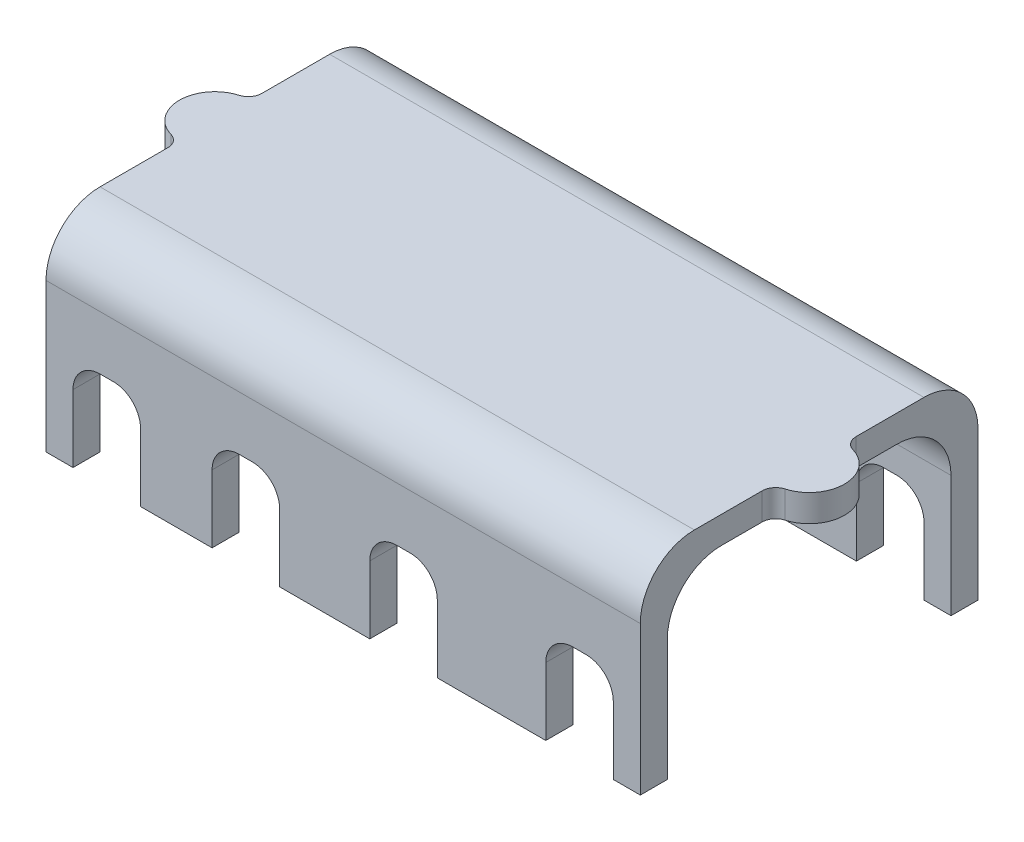
SolidWorks part; units mm, degrees
ref_plane "Plano frontal" through (0, 0, 0) normal (0, 0, 1) x (1, 0, 0)
ref_plane "Plano superior" through (0, 0, 0) normal (0, 1, 0) x (1, 0, 0)
ref_plane "Plano direito" through (0, 0, 0) normal (1, 0, 0) x (0, 0, -1)
sketch "Esboço1" plane through (0, 0, 0) normal (0, 1, 0) x (1, 0, 0)
  line L1 (-22, -12.5) -> (22, -12.5)
  line L2 (-22, -12.5) -> (-22, 12.5)
  line L3 (-22, 12.5) -> (22, 12.5)
  line L4 (22, -12.5) -> (22, 12.5)
  line L5 (-22, -12.5) -> (22, 12.5) construction
  line L6 (-22, 12.5) -> (22, -12.5) construction
  point P0 (0, 0)
  dimension "D1" = 44
  dimension "D2" = 25
extrude "Ressalto-extrusão1" add sketch "Esboço1" along normal mid plane 15
shell "Casca1" thickness 2 removed face at (0, -7.5, 0) removed face at (-22, 0, 0) removed face at (22, 0, 0)
sketch "Esboço2" plane through (0, 0, 12.5) normal (0, 0, 1) x (1, 0, 0)
  line L0 (22, 7.5) -> (22, -7.5) construction
  line L5 (-9.7033, -14.5) -> (-4.7033, -14.5)
  line L6 (-9.7033, -14.5) -> (-9.7033, -0.5)
  line L7 (-22, -7.5) -> (22, -7.5) construction
  line L8 (-20, -14.5) -> (-15, -14.5)
  line L9 (-20, -14.5) -> (-20, -0.5)
  line L10 (-20, -0.5) -> (-15, -0.5)
  line L11 (-15, -14.5) -> (-15, -0.5)
  line L12 (-20, -14.5) -> (-15, -0.5) construction
  line L13 (-20, -0.5) -> (-15, -14.5) construction
  line L14 (-22, 7.5) -> (-22, -7.5) construction
  line L15 (-9.7033, -0.5) -> (-4.7033, -0.5)
  line L16 (-4.7033, -14.5) -> (-4.7033, -0.5)
  line L17 (-9.7033, -14.5) -> (-4.7033, -0.5) construction
  line L18 (-9.7033, -0.5) -> (-4.7033, -14.5) construction
  line L19 (1.9702, -14.5) -> (6.9702, -14.5)
  line L20 (1.9702, -14.5) -> (1.9702, -0.5)
  line L21 (1.9702, -0.5) -> (6.9702, -0.5)
  line L22 (6.9702, -14.5) -> (6.9702, -0.5)
  line L23 (1.9702, -14.5) -> (6.9702, -0.5) construction
  line L24 (1.9702, -0.5) -> (6.9702, -14.5) construction
  line L25 (15, -14.5) -> (20, -14.5)
  line L26 (15, -14.5) -> (15, -0.5)
  line L27 (15, -0.5) -> (20, -0.5)
  line L28 (20, -14.5) -> (20, -0.5)
  line L29 (15, -14.5) -> (20, -0.5) construction
  line L30 (15, -0.5) -> (20, -14.5) construction
  point P0 (-17.5, -7.5)
  point P9 (-7.2033, -7.5)
  point P14 (4.4702, -7.5)
  point P19 (17.5, -7.5)
  dimension "D2" = 5
  dimension "D3" = 7
  dimension "D1" = 2
  dimension "D4" = 2
extrude "Corte-extrusão1" cut sketch "Esboço2" against normal through all
fillet "Filete1" radius 2 16 edges at (15, -0.5, 11.5) (15, -0.5, -11.5) (20, -0.5, 11.5) (20, -0.5, -11.5) (1.9702, -0.5, 11.5) (1.9702, -0.5, -11.5) (6.9702, -0.5, 11.5) (6.9702, -0.5, -11.5) (-9.7033, -0.5, 11.5) (-9.7033, -0.5, -11.5) (-4.7033, -0.5, 11.5) (-4.7033, -0.5, -11.5) (-15, -0.5, 11.5) (-15, -0.5, -11.5) (-20, -0.5, -11.5) (-20, -0.5, 11.5)
fillet "Filete2" radius 4 4 edges at (0, 7.5, -12.5) (0, 7.5, 12.5) (0, 5.5, 10.5) (0, 5.5, -10.5)
sketch "Esboço5" plane through (0, 7.5, 0) normal (0, 1, 0) x (1, 0, 0)
  line L0 (-22, -1.619) -> (-22, -2.619)
  line L1 (-22, -2.619) -> (-22, -1.619)
  line L2 (-22, 1.619) -> (-22, 2.619)
  line L3 (-22, 8.5) -> (-22, -8.5) construction
  line L4 (-22, -1.619) -> (-22, 1.619)
  line L5 (0, -8.25) -> (0, 8.25) construction
  line L6 (22, -1.619) -> (22, 1.619)
  line L7 (22, 1.619) -> (22, 2.619)
  line L8 (22, -2.619) -> (22, -1.619)
  line L9 (22, -1.619) -> (22, -2.619)
  arc A0 (-22, 2.619) -> (-22, -2.619) centre (-22, 0) ccw
  arc A2 (22, 2.619) -> (22, -2.619) centre (22, 0) cw
  line M10 (22, -8.5) -> (22, 8.5)
  line M12 (-22, 8.5) -> (-22, -8.5)
extrude "Ressalto-extrusão4" add sketch "Esboço5" against normal up to surface (2 mm away) separate body contours A0 M12 | A2 M10 region at (-23.1115, 7.5, 0) region at (23.1115, 7.5, 0) up to face at (0, 5.5, 0)
combine bodies "Combinar1" operation type add bodies to combine 102 108 110
sketch "Esboço3" [suppressed] plane through (-22, 0, 0) normal (1, 0, 0) x (0, 0, -1)
  line L0 (10.5, -7.5) -> (8.5, -7.5)
  line L2 (12.5, -8.5) -> (12.5, -7.5)
  line L3 (0, 5.5) -> (0, -5.9035) construction
  line L4 (6.5, 5.5) -> (-6.5, 5.5) construction
  line L8 (10.5, -7.5) -> (12.5, -7.5)
  line L10 (8.5, -7.5) -> (8.5, -8)
  line L11 (8.5, -8) -> (12.5, -8.5)
  line L12 (-8.5, -8) -> (-12.5, -8.5)
  line L13 (-8.5, -7.5) -> (-8.5, -8)
  line L14 (-10.5, -7.5) -> (-12.5, -7.5)
  line L15 (-12.5, -8.5) -> (-12.5, -7.5)
  line L16 (-10.5, -7.5) -> (-8.5, -7.5)
  dimension "D1" = 2
  dimension "D2" = 1
  dimension "D3" = 0.5
fillet "Filete4" radius 1 4 edges at (-22, 6.5, -2.619) (-22, 6.5, 2.619) (22, 6.5, -2.619) (22, 6.5, 2.619)
move or copy body "Corpo-Converter em corpo de malha1" [suppressed] bodies to move or copy 109 copy no translate (0, 0, 0) parameters "D1"=0, "D2"=0, "D3"=0
